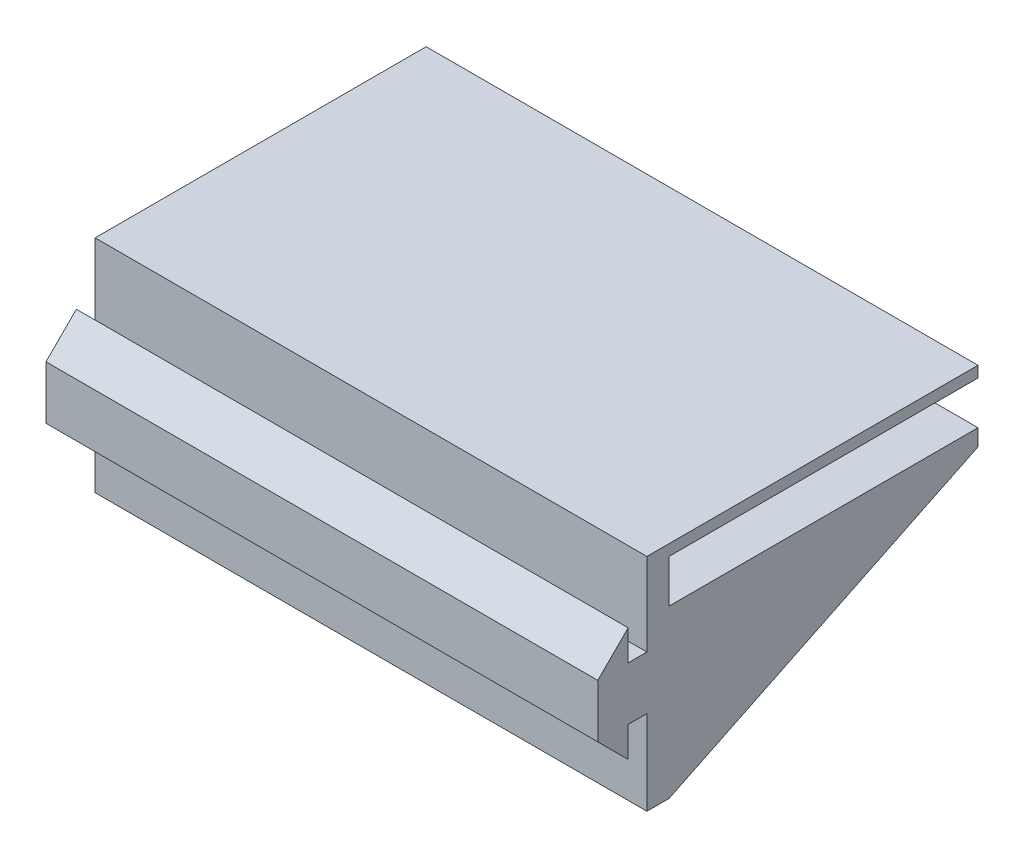
SolidWorks part; units mm, degrees
ref_plane "Front Plane" through (0, 0, 0) normal (0, 0, 1) x (1, 0, 0)
ref_plane "Top Plane" through (0, 0, 0) normal (0, 1, 0) x (1, 0, 0)
ref_plane "Right Plane" through (0, 0, 0) normal (1, 0, 0) x (0, 0, -1)
sketch "Sketch1" plane through (0, 0, 0) normal (1, 0, 0) x (0, 0, -1)
  line L0 (0, 0) -> (0, 20)
  line L1 (0, 20) -> (30, 20)
  line L2 (30, 20) -> (30, 19)
  line L3 (2, 0) -> (2, 13.6)
  line L4 (30, 13.6) -> (2, 0)
  line L5 (2, 0) -> (0, 0)
  line L6 (0, 10) -> (2, 10) construction
  line L7 (0, 10) -> (-1.7, 10) construction
  line L8 (30, 19) -> (2, 19)
  line L9 (2, 19) -> (2, 15.1)
  line L10 (2, 15.1) -> (30, 15.1)
  line L11 (30, 15.1) -> (30, 13.6)
  line L12 (30, 13.6) -> (2, 13.6)
  line L13 (-1.7, 10) -> (-1.7, 12.5) construction
  line L14 (-1.7, 12.5) -> (-1.7, 15.25)
  line L15 (-1.7, 15.25) -> (-4.45, 12.5)
  line L16 (-1.7, 10) -> (-1.7, 7.6717) construction
  line L17 (-1.7, 7.6717) -> (-1.7, 4.9217)
  line L18 (-1.7, 4.9217) -> (-4.45, 7.6717)
  line L19 (-4.45, 12.5) -> (-4.45, 7.6717)
  line L20 (-1.7, 12.5) -> (0, 12.5)
  line L21 (-1.7, 7.6717) -> (0, 7.6717)
  dimension "D1" = 20
  dimension "D4" = 2
  dimension "D5" = 30
extrude "Boss-Extrude2" add sketch "Sketch1" along normal blind 50 contours L0 L6 L1 | L17 L21 L0 L20 L14 L15 L19 L18 region at (0, 14.0791, -10.5455) region at (0, 10.0858, 2.327)
extrude "Boss-Extrude10" add sketch "Sketch1<13>" along normal blind 1.5 contours L4 L12 L3 region at (0, 9.0667, -11.3333)
sketch "Sketch1<13>" plane through (0, 0, 0) normal (1, 0, 0) x (0, 0, -1) same geometry as "Sketch1"
sketch "Sketch7" plane through (50, 0, 0) normal (1, 0, 0) x (0, 0, -1)
  line L0 (2, 13.6) -> (2, 0)
  line L1 (2, 0) -> (30, 13.6)
  line L2 (30, 13.6) -> (2, 13.6) construction
  line L3 (30, 13.6) -> (2, 13.6)
extrude "Boss-Extrude11" add sketch "Sketch7" against normal blind 1.5
